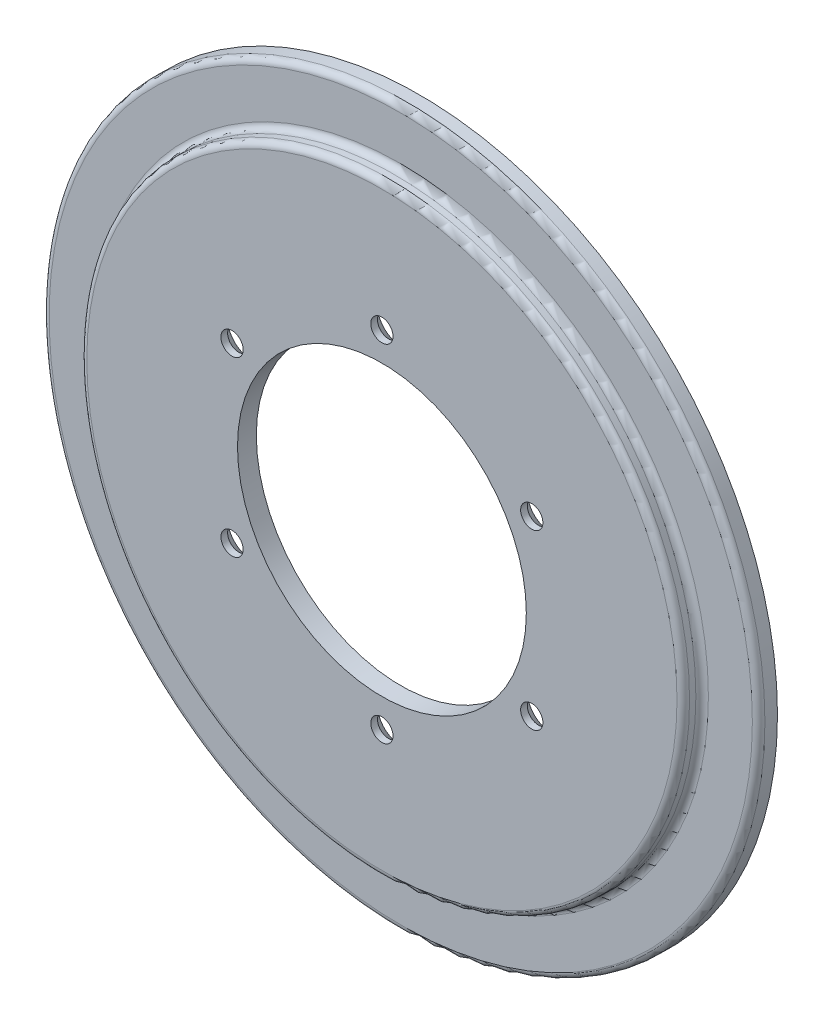
SolidWorks part; units mm, degrees
ref_plane "Front Plane" through (0, 0, 0) normal (0, 0, 1) x (1, 0, 0)
ref_plane "Top Plane" through (0, 0, 0) normal (0, 1, 0) x (1, 0, 0)
ref_plane "Right Plane" through (0, 0, 0) normal (1, 0, 0) x (0, 0, -1)
sketch "Sketch3" plane through (0, 0, 0) normal (1, 0, 0) x (0, 0, -1)
  line L0 (0, 29.21) -> (0, 59.69)
  line L1 (1.27, 60.96) -> (2.54, 60.96)
  line L2 (3.81, 62.23) -> (3.81, 71.12)
  line L3 (5.08, 72.39) -> (7.62, 72.39)
  line L4 (7.62, 72.39) -> (7.62, 58.42)
  line L5 (6.35, 57.15) -> (5.08, 57.15)
  line L6 (3.81, 55.88) -> (3.81, 29.21)
  line L7 (3.81, 29.21) -> (0, 29.21)
  line L8 (0, 0) -> (50000, 0) construction
  arc A0 (3.81, 71.12) -> (5.08, 72.39) centre (5.08, 71.12) cw
  arc A1 (2.54, 60.96) -> (3.81, 62.23) centre (2.54, 62.23) ccw
  arc A2 (0, 59.69) -> (1.27, 60.96) centre (1.27, 59.69) cw
  arc A3 (5.08, 57.15) -> (3.81, 55.88) centre (5.08, 55.88) ccw
  arc A4 (7.62, 58.42) -> (6.35, 57.15) centre (6.35, 58.42) cw
  dimension "D7" = 1.27
  dimension "D1" = 72.39
  dimension "D2" = 60.96
  dimension "D3" = 29.21
  dimension "D4" = 3.81
  dimension "D5" = 7.62
  dimension "D6" = 57.15
revolve "Revolve1" add sketch "Sketch3" angle 360 about L8
sketch "Sketch6" plane through (0, 0, -3.81) normal (0, 0, -1) x (-1, 0, 0)
  point P0 (0, 35)
  point P1 (0, 0)
  point P3 (0, 0)
  dimension "D1" = 35
hole_wizard "CSK for M4 Countersunk Flat Head Screw2" positions "Sketch6" profile "Sketch7" countersink size "M4" standard "ISO"
sketch "Sketch7" plane through (0, 35, -3.81) normal (1, 0, 0) x (0, 1, 0)
  line L0 (0, 0) -> (0, 5.1619)
  line L1 (0, 5.1619) -> (2.25, 3.81)
  line L2 (2.25, 3.81) -> (2.25, 2.45)
  line L3 (2.25, 2.45) -> (4.7, 0)
  line L5 (4.7, 0) -> (0, 0)
  line L6 (-2.25, 2.45) -> (-4.7, 0) construction
  line L10 (0, 5.1619) -> (-2.25, 3.81) construction
  line L11 (0, -6.35) -> (0, 107.95) construction
  dimension "Hole Dia." = 4.5
  dimension "Hole Depth" = 3.81
  dimension "Near C'Sink Dia." = 9.4
  dimension "Near C'Sink Angle" = 90
  dimension "Drill Angle" = 118
pattern_circular "CirPattern2" count 6 over 360 about axis through (0, 0, -3.81) along (0, 0, 1) of "CSK for M4 Countersunk Flat Head Screw2"
